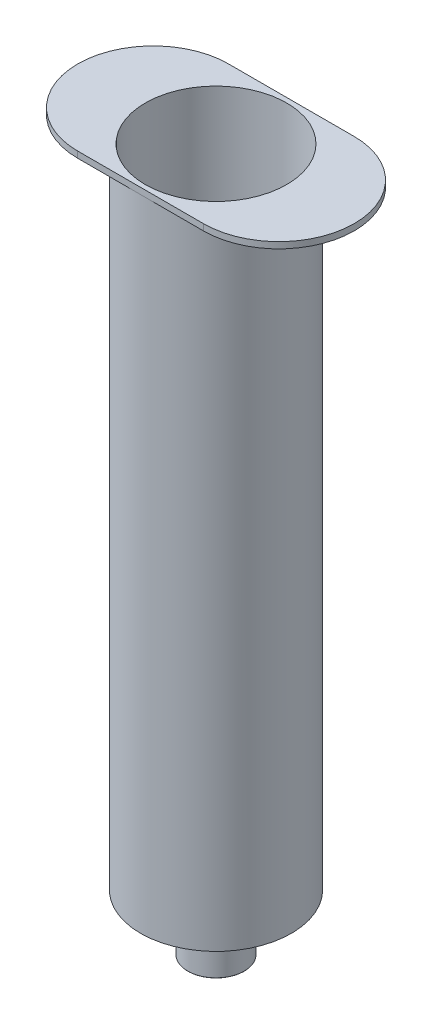
SolidWorks part; units mm, degrees
ref_plane "Front Plane" through (0, 0, 0) normal (0, 0, 1) x (1, 0, 0)
ref_plane "Top Plane" through (0, 0, 0) normal (0, 1, 0) x (1, 0, 0)
ref_plane "Right Plane" through (0, 0, 0) normal (1, 0, 0) x (0, 0, -1)
sketch "Sketch1" plane through (0, 0, 0) normal (0, 1, 0) x (1, 0, 0)
  circle A0 centre (0, 0) radius 12
  dimension "D1" = 24
extrude "Boss-Extrude1" add sketch "Sketch1" along normal blind 105
sketch "Sketch2" plane through (0, 105, 0) normal (0, 1, 0) x (1, 0, 0)
  circle A0 centre (0, 0) radius 11.25
  dimension "D1" = 22.5
extrude "Cut-Extrude2" cut sketch "Sketch2" against normal blind 102
chamfer "Chamfer3" distance 12 angle 15 1 edges at (0, 0, 12) first distance on face at (0, 0, 12)
sketch "Sketch3" plane through (0, 105, 0) normal (0, 1, 0) x (1, 0, 0)
  circle A0 centre (0, 0) radius 1
  dimension "D1" = 2
extrude "Cut-Extrude3" cut sketch "Sketch3" against normal blind 116
ref_plane "Plane2" through (0, 0.2679, 0) normal (0, 1, 0) x (1, 0, 0)
sketch "Sketch4" plane through (0, 0.2679, 0) normal (0, 1, 0) x (1, 0, 0)
  circle A0 centre (0, 0) radius 4.5
  circle A1 centre (0, 0) radius 4
  dimension "D1" = 9
  dimension "D2" = 8
extrude "Boss-Extrude2" add sketch "Sketch4" along normal blind 1
sketch "Sketch5" plane through (0, 0.2679, 0) normal (0, -1, 0) x (1, 0, 0)
  circle A0 centre (0, 0) radius 4 construction
  circle A1 centre (0, 0) radius 4.5
  circle A2 centre (0, 0) radius 4.5
  circle A3 centre (0, 0) radius 4
  dimension "D1" = 0
extrude "Boss-Extrude3" add sketch "Sketch5" along normal blind 6.04
sketch "Sketch6" plane through (0, 0.2679, 0) normal (0, 1, 0) x (1, 0, 0)
  circle A0 centre (0, 0) radius 1.4
  circle A1 centre (0, 0) radius 1
  dimension "D1" = 2
  dimension "D2" = 2.8
extrude "Boss-Extrude4" add sketch "Sketch6" against normal blind 7
fillet "Fillet1" radius 0.2 1 edges at (0, -6.7321, 1.4)
fillet "Fillet2" radius 0.05 1 edges at (0, -5.7721, -4.5)
fillet "Fillet3" radius 0.05 1 edges at (0, -5.7721, -4)
sketch "Sketch7" plane through (0, 105, 0) normal (0, 1, 0) x (1, 0, 0)
  line L0 (-10, 0) -> (10, 0) construction
  line L1 (-10, 12) -> (10, 12)
  line L2 (-10, -12) -> (10, -12)
  arc A0 (-10, 12) -> (-10, -12) centre (-10, 0) ccw
  arc A1 (10, -12) -> (10, 12) centre (10, 0) ccw
  circle A2 centre (0, 0) radius 11.25 construction
  circle A3 centre (0, 0) radius 11.25
  point P2 (0, 0)
  dimension "D1" = 24
  dimension "D2" = 10
extrude "Boss-Extrude5" add sketch "Sketch7" along normal blind 1
